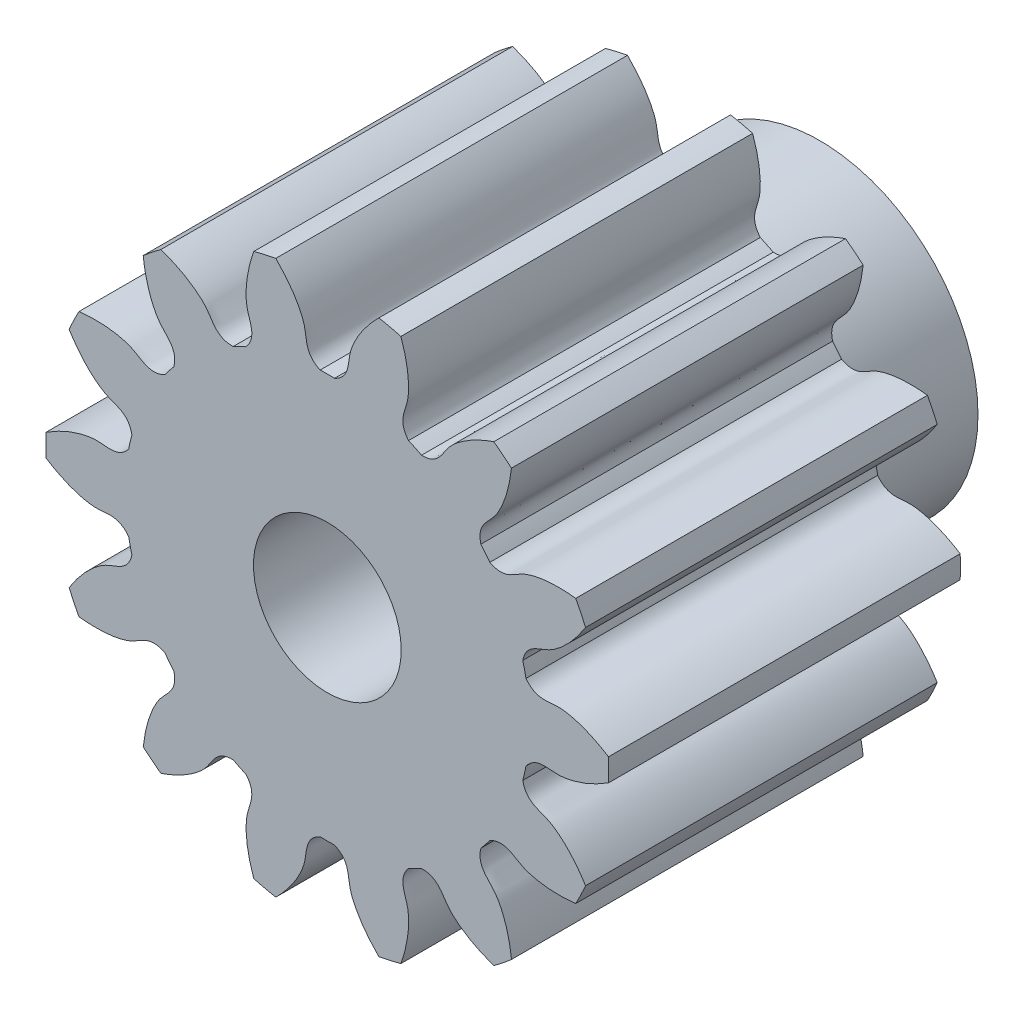
SolidWorks part; units mm, degrees
ref_plane "前视基准面" through (0, 0, 0) normal (0, 0, 1) x (1, 0, 0)
ref_plane "上视基准面" through (0, 0, 0) normal (0, 1, 0) x (1, 0, 0)
ref_plane "右视基准面" through (0, 0, 0) normal (1, 0, 0) x (0, 0, -1)
other "Configuration Table"
sketch "草图1" plane through (0, 0, 0) normal (0, 0, 1) x (1, 0, 0)
  circle A0 centre (0, 0) radius 4
extrude "凸台-拉伸1" add sketch "草图1" along normal blind 5
ref_axis "基准轴1" through (0, 0, 5) along (0, 0, -1)
sketch "草图2" plane through (0, 0, 0) normal (0, 0, 1) x (1, 0, 0)
  line L0 (0, 0) -> (0, 4) construction
  circle A0 centre (0, 0) radius 4 construction
  arc A1 (0.1022, 2.8732) -> (-0.1022, 2.8732) centre (0, 0) ccw
  arc A2 (1.612, 4.5136) -> (-1.612, 4.5136) centre (0, 0) ccw
  spline S0 degree 3 poles (0.1022, 2.8732) (0.3233, 2.974) (0.2859, 3.1585) (0.3318, 3.3257) (0.3354, 3.3377) (0.3396, 3.3509) (0.3444, 3.3652) (0.3501, 3.3806) (0.3564, 3.3972) (0.3637, 3.4149) (0.3717, 3.4336) (0.3808, 3.4533) (0.3907, 3.4741) (0.4017, 3.4958) (0.4137, 3.5185) (0.4268, 3.542) (0.4411, 3.5665) (0.4565, 3.5918) (0.4731, 3.6178) (0.491, 3.6446) (0.5101, 3.6722) (0.5306, 3.7004) (0.5525, 3.7293) (0.5757, 3.7587) (0.6003, 3.7887) (0.6264, 3.8192) (0.654, 3.8501) (0.683, 3.8815) (0.7136, 3.9132) (0.7458, 3.9452) (0.7796, 3.9775) (0.8149, 4.01) (0.8519, 4.0426) (0.8905, 4.0754) (0.9309, 4.1082) (0.9728, 4.141) (1.0165, 4.1737) (1.0619, 4.2064) (1.1091, 4.2388) (1.1579, 4.2711) (1.2086, 4.303) (1.2609, 4.3346) (1.3151, 4.3659) (1.371, 4.3966) (1.4286, 4.4269) (1.5087, 4.4669) (1.5702, 4.4953) (1.612, 4.5136) knots 0 0 0 0 0.215624 0.220482 0.225911 0.231912 0.238484 0.245628 0.253343 0.26163 0.270488 0.279917 0.289919 0.300491 0.311635 0.323351 0.335638 0.348497 0.361927 0.375928 0.390502 0.405646 0.421362 0.43765 0.454509 0.471939 0.489942 0.508515 0.52766 0.547377 0.567665 0.588524 0.609955 0.631958 0.654532 0.677677 0.701394 0.725683 0.750543 0.775974 0.801977 0.828552 0.855698 0.883415 0.911704 0.940565 1 1 1 1
  spline S1 degree 3 poles (-0.1022, 2.8732) (-0.3233, 2.974) (-0.2859, 3.1585) (-0.3318, 3.3257) (-0.3354, 3.3377) (-0.3396, 3.3509) (-0.3444, 3.3652) (-0.3501, 3.3806) (-0.3564, 3.3972) (-0.3637, 3.4149) (-0.3717, 3.4336) (-0.3808, 3.4533) (-0.3907, 3.4741) (-0.4017, 3.4958) (-0.4137, 3.5185) (-0.4268, 3.542) (-0.4411, 3.5665) (-0.4565, 3.5918) (-0.4731, 3.6178) (-0.491, 3.6446) (-0.5101, 3.6722) (-0.5306, 3.7004) (-0.5525, 3.7293) (-0.5757, 3.7587) (-0.6003, 3.7887) (-0.6264, 3.8192) (-0.654, 3.8501) (-0.683, 3.8815) (-0.7136, 3.9132) (-0.7458, 3.9452) (-0.7796, 3.9775) (-0.8149, 4.01) (-0.8519, 4.0426) (-0.8905, 4.0754) (-0.9309, 4.1082) (-0.9728, 4.141) (-1.0165, 4.1737) (-1.0619, 4.2064) (-1.1091, 4.2388) (-1.1579, 4.2711) (-1.2086, 4.303) (-1.2609, 4.3346) (-1.3151, 4.3659) (-1.371, 4.3966) (-1.4286, 4.4269) (-1.5087, 4.4669) (-1.5702, 4.4953) (-1.612, 4.5136) knots 0 0 0 0 0.215624 0.220482 0.225911 0.231912 0.238484 0.245628 0.253343 0.26163 0.270488 0.279917 0.289919 0.300491 0.311635 0.323351 0.335638 0.348497 0.361927 0.375928 0.390502 0.405646 0.421362 0.43765 0.454509 0.471939 0.489942 0.508515 0.52766 0.547377 0.567665 0.588524 0.609955 0.631958 0.654532 0.677677 0.701394 0.725683 0.750543 0.775974 0.801977 0.828552 0.855698 0.883415 0.911704 0.940565 1 1 1 1
extrude "切除-拉伸1" cut sketch "草图2" along normal through all
pattern_circular "阵列(圆周)1" count 14 every 25.714 about axis through (0, 0, 5) along (0, 0, -1) of "切除-拉伸1"
sketch "草图3" plane through (0, 0, 0) normal (0, 0, 1) x (1, 0, 0)
  circle A0 centre (0, 0) radius 3.5 construction
  dimension "Dn" = 7
sketch "草图4" plane through (0, 0, 0) normal (0, 0, -1) x (-1, 0, 0)
  circle A0 centre (0, 0) radius 1.05
  circle A1 centre (0, 0) radius 2.25
  dimension "D1" = 2.1
  dimension "D2" = 1.2
extrude "凸台-拉伸2" add sketch "草图4" along normal blind 2
sketch "草图5" plane through (0, 0, 0) normal (0, 0, -1) x (-1, 0, 0)
  circle A0 centre (0, 0) radius 1.05 construction
  circle A1 centre (0, 0) radius 1.05
extrude "切除-拉伸2" cut sketch "草图5" against normal up to next
